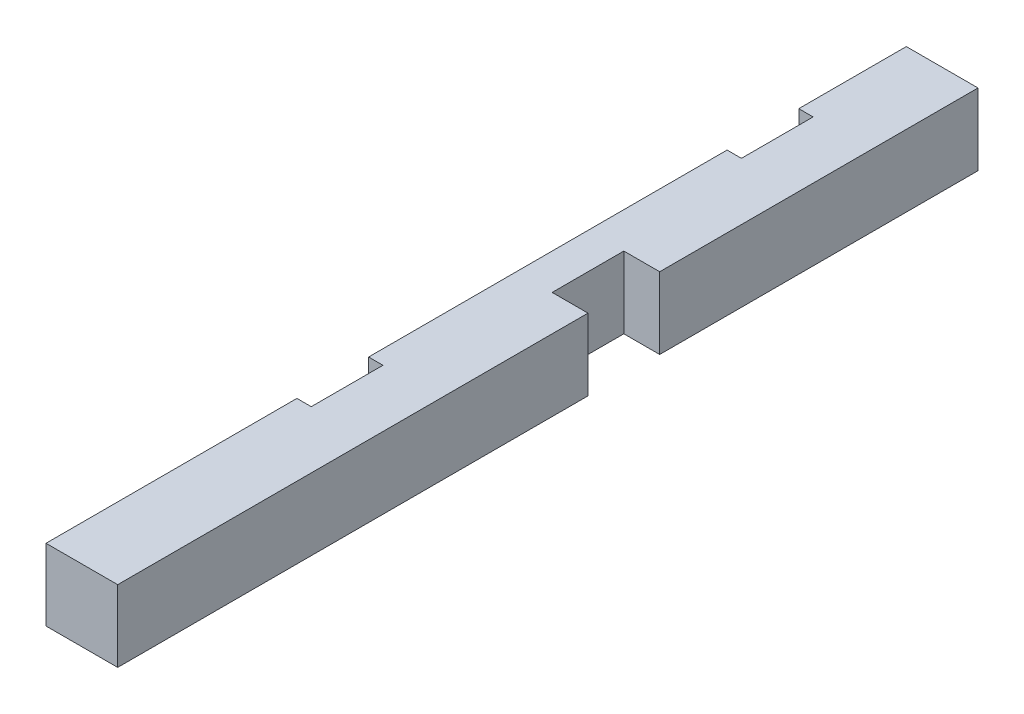
SolidWorks part; units mm, degrees
ref_plane "Plan de face" through (0, 0, 0) normal (0, 0, 1) x (1, 0, 0)
ref_plane "Plan de dessus" through (0, 0, 0) normal (0, 1, 0) x (1, 0, 0)
ref_plane "Plan de droite" through (0, 0, 0) normal (1, 0, 0) x (0, 0, -1)
sketch "Esquisse1" plane through (0, 0, 0) normal (0, 0, 1) x (1, 0, 0)
  line L1 (0, 0) -> (10, 0)
  line L2 (0, 0) -> (0, 10)
  line L3 (0, 10) -> (10, 10)
  line L4 (10, 0) -> (10, 10)
  dimension "D1" = 10
  dimension "D2" = 10
extrude "Boss.-Extru.1" add sketch "Esquisse1" along normal blind 120
sketch "Esquisse2" plane through (0, 10, 0) normal (0, 1, 0) x (1, 0, 0)
  line L0 (10, -120) -> (10, 0) construction
  line L1 (10, -44.4) -> (5, -44.4)
  line L2 (10, -44.4) -> (10, -54.4)
  line L3 (10, -54.4) -> (5, -54.4)
  line L4 (5, -44.4) -> (5, -54.4)
  line L5 (10, 0) -> (0, 0) construction
  point P6 (7.5, -44.4)
  point P9 (5, 0)
  dimension "D1" = 44.4
  dimension "D2" = 10
  dimension "D3" = 5
extrude "Enlèv. mat.-Extru.1" cut sketch "Esquisse2" against normal through all
sketch "Esquisse3" plane through (0, 0, 0) normal (-1, 0, 0) x (0, 0, 1)
  line L0 (120, 0) -> (0, 0) construction
  line L1 (85, 0) -> (75, 0)
  line L2 (85, 0) -> (85, 10)
  line L3 (85, 10) -> (75, 10)
  line L4 (75, 0) -> (75, 10)
  line L5 (120, 10) -> (0, 10) construction
  line L6 (120, 10) -> (120, 0) construction
  dimension "D1" = 10
  dimension "D2" = 35
extrude "Enlèv. mat.-Extru.2" cut sketch "Esquisse3" against normal blind 2
sketch "Esquisse4" plane through (0, 0, 0) normal (0, -1, 0) x (1, 0, 0)
  line L0 (0, 75) -> (0, 0) construction
  line L1 (2, 25) -> (0, 25)
  line L2 (2, 25) -> (2, 15)
  line L3 (2, 15) -> (0, 15)
  line L4 (0, 25) -> (0, 15)
  line L5 (0, 0) -> (10, 0) construction
  point P8 (5, 0)
  dimension "D1" = 10
  dimension "D2" = 2
  dimension "D3" = 15
extrude "Enlèv. mat.-Extru.3" cut sketch "Esquisse4" against normal through all
